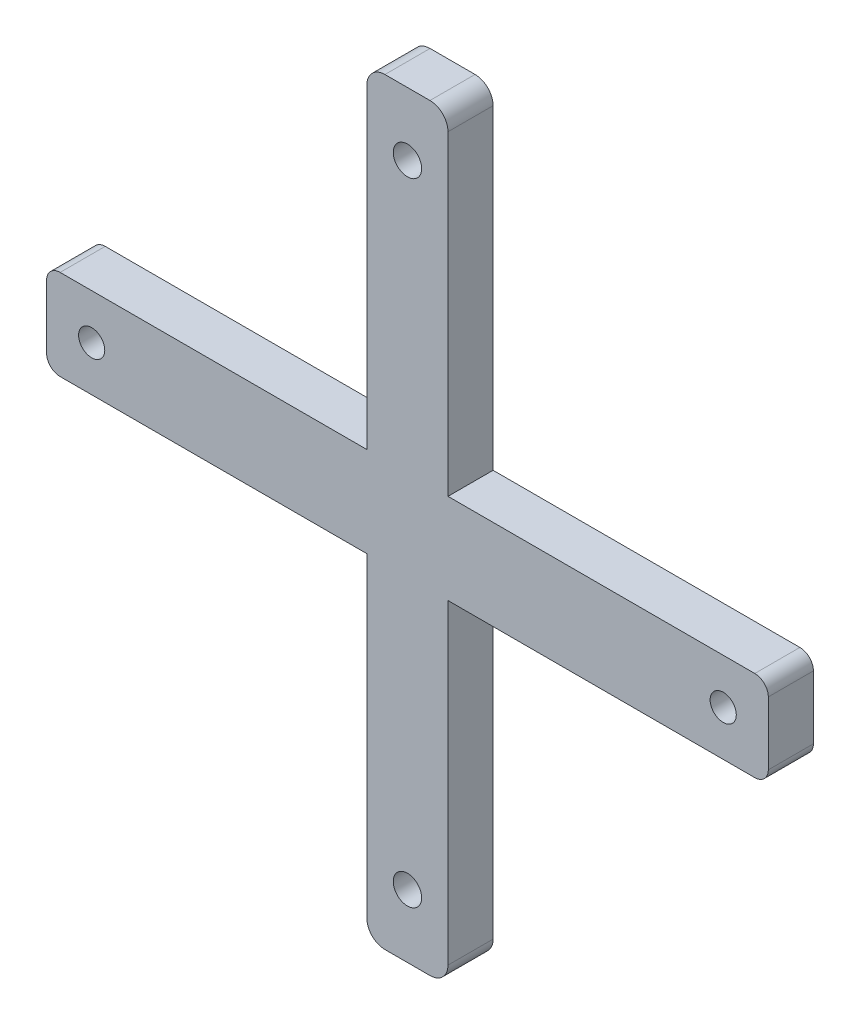
SolidWorks part; units mm, degrees
ref_plane "Front Plane" through (0, 0, 0) normal (0, 0, 1) x (1, 0, 0)
ref_plane "Top Plane" through (0, 0, 0) normal (0, 1, 0) x (1, 0, 0)
ref_plane "Right Plane" through (0, 0, 0) normal (1, 0, 0) x (0, 0, -1)
sketch "Sketch1" plane through (0, 0, 0) normal (0, 0, 1) x (1, 0, 0)
  line L1 (97.79, -12.7) -> (-97.79, -12.7)
  line L2 (101.6, -8.89) -> (101.6, 8.89)
  line L3 (97.79, 12.7) -> (-97.79, 12.7)
  line L4 (-101.6, -8.89) -> (-101.6, 8.89)
  line L5 (101.6, -12.7) -> (-101.6, 12.7) construction
  line L6 (101.6, 12.7) -> (-101.6, -12.7) construction
  arc A0 (101.6, 8.89) -> (97.79, 12.7) centre (97.79, 8.89) ccw
  arc A1 (97.79, -12.7) -> (101.6, -8.89) centre (97.79, -8.89) ccw
  arc A2 (-97.79, -12.7) -> (-101.6, -8.89) centre (-97.79, -8.89) cw
  arc A3 (-97.79, 12.7) -> (-101.6, 8.89) centre (-97.79, 8.89) ccw
  circle A4 centre (-88.9, 0) radius 3.683
  circle A5 centre (88.9, 0) radius 3.683
  point P0 (0, 0)
  dimension "D3" = 3.81
  dimension "D6" = 7.366
  dimension "D7" = 7.366
  dimension "D1" = 25.4
  dimension "D2" = 203.2
  dimension "D4" = 88.9
  dimension "D5" = 88.9
extrude "Boss-Extrude1" add sketch "Sketch1" along normal blind 12.7
sketch "Sketch3" plane through (0, 0, 12.7) normal (0, 0, 1) x (1, 0, 0)
  line L1 (-6.3354, -106.68) -> (6.3354, -106.68)
  line L2 (-11.4154, -101.6) -> (-11.4154, 101.6)
  line L3 (-6.3354, 106.68) -> (6.3354, 106.68)
  line L4 (11.4154, -101.6) -> (11.4154, 101.6)
  line L5 (-11.4154, -106.68) -> (11.4154, 106.68) construction
  line L6 (-11.4154, 106.68) -> (11.4154, -106.68) construction
  arc A0 (-6.3354, -106.68) -> (-11.4154, -101.6) centre (-6.3354, -101.6) cw
  arc A1 (6.3354, -106.68) -> (11.4154, -101.6) centre (6.3354, -101.6) ccw
  arc A2 (-11.4154, 101.6) -> (-6.3354, 106.68) centre (-6.3354, 101.6) cw
  arc A3 (6.3354, 106.68) -> (11.4154, 101.6) centre (6.3354, 101.6) cw
  circle A4 centre (0, 88.9) radius 4
  circle A5 centre (0, -88.9) radius 4
  point P0 (0, 0)
  dimension "D1" = 5.08
  dimension "D3" = 88.9
  dimension "D5" = 8
  dimension "D6" = 8
  dimension "D2" = 88.9
  dimension "D4" = 203.2
extrude "Boss-Extrude3" add sketch "Sketch3" against normal through all
sketch "Sketch2" plane through (0, 0, 0) normal (0, 0, -1) x (-1, 0, 0)
  circle A0 centre (-88.9, 0) radius 3.683
  circle A1 centre (88.9, 0) radius 3.683
  circle A2 centre (0, 88.9) radius 4
  circle A3 centre (0, -88.9) radius 4
extrude "Boss-Extrude2" add sketch "Sketch2" against normal blind 6.35
